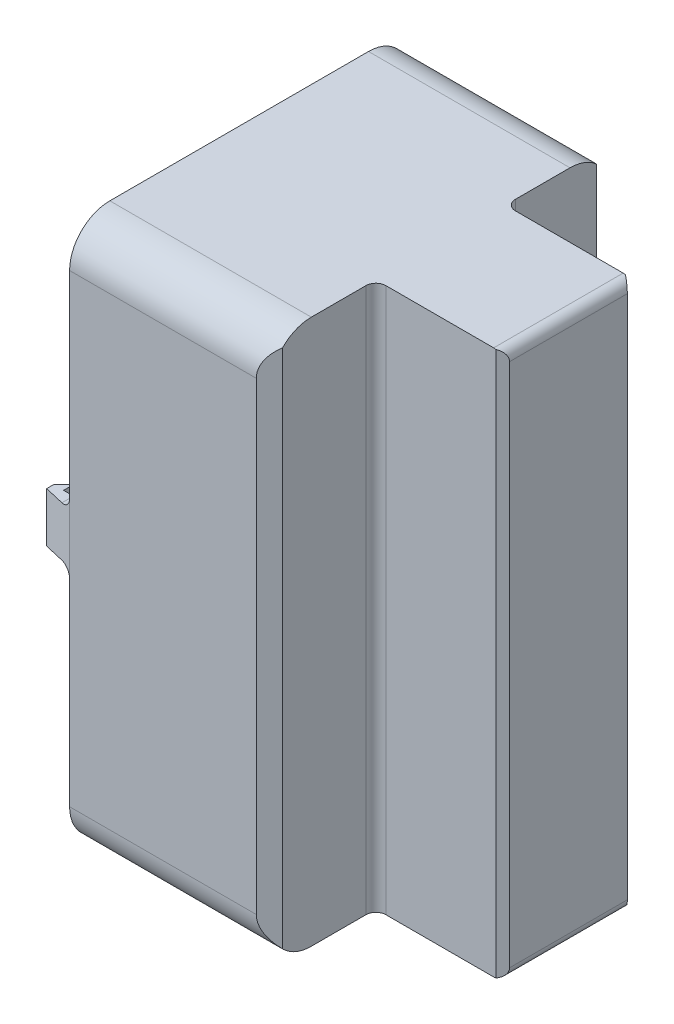
SolidWorks part; units mm, degrees
ref_plane "Top Plane" through (0, 0, 0) normal (0, 0, 1) x (1, 0, 0)
ref_plane "Right Plane" through (0, 0, 0) normal (0, 1, 0) x (1, 0, 0)
ref_plane "Front Plane" through (0, 0, 0) normal (1, 0, 0) x (0, 0, -1)
ref_axis "x-axis" through (-88.99, 0, 0) along (1, 0, 0)
ref_axis "y-axis" through (0, -55, 0) along (0, 1, 0)
ref_axis "z-axis" through (0, 0, 55) along (0, 0, -1)
sketch "Sketch2" plane through (0, 0, 0) normal (1, 0, 0) x (0, -1, 0)
  line L0 (-980.3227, 1369.3053) -> (-980.3227, 1357.3053) construction
  line L1 (-1019.3227, 1357.3053) -> (-1019.3227, 1369.3053) construction
  line L2 (-980.3227, 1357.3053) -> (-1019.3227, 1357.3053) construction
  line L3 (-1018.3227, 1369.3053) -> (-981.3227, 1369.3053) construction
  line L12 (-980.3227, 1369.3053) -> (-980.3227, 1357.3053)
  line L13 (-980.3227, 1357.3053) -> (-1019.3227, 1357.3053)
  line L14 (-1019.3227, 1357.3053) -> (-1019.3227, 1369.3053)
  line L15 (-1019.3227, 1369.3053) -> (-980.3227, 1369.3053)
  line L29 (-1027.1727, 1376.2903) -> (-1027.1727, 1350.3203)
  line L30 (-976.5127, 1380.3303) -> (-1023.1327, 1380.3303)
  line L31 (-972.4727, 1350.3203) -> (-972.4727, 1376.2903)
  line L32 (-1023.1327, 1346.2803) -> (-976.5127, 1346.2803)
  line L33 (-1027.1727, 1376.2903) -> (-1027.1727, 1350.3203)
  line L34 (-976.5127, 1380.3303) -> (-1023.1327, 1380.3303)
  line L35 (-972.4727, 1350.3203) -> (-972.4727, 1376.2903)
  line L36 (-1023.1327, 1346.2803) -> (-976.5127, 1346.2803)
  arc A20 (-1027.1727, 1350.3203) -> (-1023.1327, 1346.2803) centre (-1023.1327, 1350.3203) ccw
  arc A21 (-1023.1327, 1380.3303) -> (-1027.1727, 1376.2903) centre (-1023.1327, 1376.2903) ccw
  arc A22 (-972.4727, 1376.2903) -> (-976.5127, 1380.3303) centre (-976.5127, 1376.2903) ccw
  arc A23 (-976.5127, 1346.2803) -> (-972.4727, 1350.3203) centre (-976.5127, 1350.3203) ccw
  arc A24 (-1027.1727, 1350.3203) -> (-1023.1327, 1346.2803) centre (-1023.1327, 1350.3203) ccw
  arc A25 (-1023.1327, 1380.3303) -> (-1027.1727, 1376.2903) centre (-1023.1327, 1376.2903) ccw
  arc A26 (-972.4727, 1376.2903) -> (-976.5127, 1380.3303) centre (-976.5127, 1376.2903) ccw
  arc A27 (-976.5127, 1346.2803) -> (-972.4727, 1350.3203) centre (-976.5127, 1350.3203) ccw
  dimension "D1" = 1.5
extrude "Boss-Extrude2" add sketch "Sketch2" along normal blind 13 and the other way blind 19.75
sketch "Sketch3" plane through (13, 0, 0) normal (1, 0, 0) x (0, 1, 0)
  line L0 (972.4727, -1350.3203) -> (972.4727, -1376.2903) construction
  line L1 (976.5127, -1380.3303) -> (1023.1327, -1380.3303) construction
  line L2 (1027.1727, -1376.2903) -> (1027.1727, -1350.3203) construction
  line L3 (1023.1327, -1346.2803) -> (976.5127, -1346.2803) construction
  line L4 (972.4727, -1350.3203) -> (972.4727, -1376.2903)
  line L5 (976.5127, -1380.3303) -> (1023.1327, -1380.3303)
  line L7 (1027.1727, -1376.2903) -> (1027.1727, -1350.3203)
  line L13 (1023.1327, -1346.2803) -> (976.5127, -1346.2803)
  arc A0 (976.5127, -1346.2803) -> (972.4727, -1350.3203) centre (976.5127, -1350.3203) ccw construction
  arc A1 (972.4727, -1376.2903) -> (976.5127, -1380.3303) centre (976.5127, -1376.2903) ccw construction
  arc A2 (1023.1327, -1380.3303) -> (1027.1727, -1376.2903) centre (1023.1327, -1376.2903) ccw construction
  arc A3 (1027.1727, -1350.3203) -> (1023.1327, -1346.2803) centre (1023.1327, -1350.3203) ccw construction
  arc A4 (976.5127, -1346.2803) -> (972.4727, -1350.3203) centre (976.5127, -1350.3203) ccw
  arc A6 (972.4727, -1376.2903) -> (976.5127, -1380.3303) centre (976.5127, -1376.2903) ccw
  arc A7 (1023.1327, -1380.3303) -> (1027.1727, -1376.2903) centre (1023.1327, -1376.2903) ccw
  arc A13 (1027.1727, -1350.3203) -> (1023.1327, -1346.2803) centre (1023.1327, -1350.3203) ccw
extrude "Boss-Extrude3" add sketch "Sketch3" along normal blind 0.3
sketch "Sketch6" plane through (-19.75, 0, 0) normal (-1, 0, 0) x (0, -1, 0)
  line L22 (-972.4727, -1363.3053) -> (-1027.1727, -1363.3053) construction
  line L23 (-972.4727, -1350.3203) -> (-972.4727, -1376.2903) construction
  line L24 (-1027.1727, -1376.2903) -> (-1027.1727, -1350.3203) construction
  line L26 (-1025.7727, -1350.3203) -> (-1025.7727, -1376.2903)
  line L27 (-1023.1327, -1378.9303) -> (-976.5127, -1378.9303)
  line L28 (-973.8727, -1376.2903) -> (-973.8727, -1350.3203)
  line L29 (-976.5127, -1347.6803) -> (-1023.1327, -1347.6803)
  arc A32 (-1023.1327, -1347.6803) -> (-1025.7727, -1350.3203) centre (-1023.1327, -1350.3203) ccw
  arc A33 (-1025.7727, -1376.2903) -> (-1023.1327, -1378.9303) centre (-1023.1327, -1376.2903) ccw
  arc A34 (-976.5127, -1378.9303) -> (-973.8727, -1376.2903) centre (-976.5127, -1376.2903) ccw
  arc A35 (-973.8727, -1350.3203) -> (-976.5127, -1347.6803) centre (-976.5127, -1350.3203) ccw
  point P8 (-1025.7727, -1363.3053)
  point P9 (-999.8227, -1378.9303)
  point P10 (-999.8227, -1363.3053)
  dimension "D3" = 2.64
  dimension "D1" = 31.25
  dimension "D2" = 51.9
extrude "Cut-Extrude1" cut sketch "Sketch6" against normal offset from surface (19.727 mm away) 0.1 offset beyond the face yes
ref_plane "Plane1" through (0, 999.8227, 0) normal (0, -1, 0) x (-1, 0, 0)
ref_plane "Plane2" through (0, 0, -1363.3053) normal (0, 0, -1) x (-1, 0, 0)
sketch "Sketch10" plane through (0, 999.8227, 0) normal (0, -1, 0) x (-1, 0, 0)
  line L22 (19.75, 1346.2803) -> (19.75, 1347.6803)
  line L23 (19.75, 1347.6803) -> (21.75, 1347.6803)
  line L24 (21.75, 1347.6803) -> (21.75, 1348.6803)
  line L25 (21.75, 1348.6803) -> (22.75, 1347.6803)
  line L26 (22.75, 1347.6803) -> (22.75, 1346.9803)
  line L27 (22.75, 1346.9803) -> (19.75, 1346.2803)
  line L28 (19.75, 1346.2803) -> (19.75, 1350.3203) construction
  line L30 (19.75, 1346.2803) -> (19.75, 1350.3203) construction
  line L31 (0.023, 1347.6803) -> (19.75, 1347.6803) construction
  point P6 (0, 0)
  point P7 (19.75, 1346.9803)
  point P8 (0, 0)
  point P9 (27.62, -1.5)
  point P12 (24, -0.5115)
  point P13 (21, -1.5)
  point P14 (21, -0.3671)
  point P15 (21, -0.3621)
  point P20 (0, 0)
  dimension "D2" = 3
  dimension "D3" = 1
  dimension "D1" = 1
ref_axis "Axis1" through (0, 999.8227, -1344.5778) along (0, 0, -1)
extrude "Clip Edge" add sketch "Sketch10" along normal mid plane 5
mirror "Mirror1" about plane through (0, 0, -1363.3053) normal (0, 0, -1) of "Clip Edge"
fillet "Fillet1" radius 1 20 edges at (13.3, 973.656, -1379.147) (13.3, 972.4727, -1363.3053) (13.3, 973.656, -1347.4636) (13.3, 999.8227, -1346.2803) (13.3, 1025.9894, -1347.4636) (13.3, 1027.1727, -1363.3053) (13.3, 1025.9894, -1379.147) (13, 999.8227, -1357.3053) (13, 980.3227, -1363.3053) (13, 999.8227, -1369.3053) (13, 1019.3227, -1363.3053) (13.3, 999.8227, -1380.3303) (-0.023, 999.8227, -1369.3053) (-0.023, 980.3227, -1363.3053) (-0.023, 999.8227, -1357.3053) (-0.023, 1019.3227, -1363.3053) (-19.75, 997.3227, -1379.6303) (-19.75, 997.3227, -1346.9803) (-19.75, 1002.3227, -1346.9803) (-19.75, 1002.3227, -1379.6303)
sketch "Sketch11" plane through (0, 1027.1727, 0) normal (0, 1, 0) x (-1, 0, 0)
  line L1 (19.75, -1380.3303) -> (-12.3, -1380.3303) construction
  line L4 (19.75, -1346.2803) -> (-12.3, -1346.2803) construction
  line L5 (-13.3, -1350.3203) -> (-13.3, -1376.2903) construction
  line L6 (19.75, -1380.3303) -> (-12.3, -1380.3303) construction
  line L7 (19.75, -1346.2803) -> (-12.3, -1346.2803) construction
  line L8 (-13.3, -1376.2903) -> (-13.3, -1350.3203) construction
  line L9 (-13.3, -1357.4019) -> (-13.3, -1350.3203)
  line L10 (-12.5325, -1369.8053) -> (-0.477, -1369.8053)
  line L11 (-0.477, -1369.8053) -> (-0.477, -1378.9652)
  line L12 (1.3197, -1380.3303) -> (-12.3, -1380.3303)
  line L13 (-13.3, -1369.2222) -> (-12.5325, -1369.8053)
  line L14 (1.0077, -1346.2803) -> (-12.3, -1346.2803)
  line L15 (-13.3, -1347.2803) -> (-13.3, -1350.3203) construction
  line L16 (-13.3, -1347.2803) -> (-13.3, -1350.3203)
  line L17 (-13.3, -1379.3303) -> (-13.3, -1369.2222)
  line L18 (-0.477, -1378.9652) -> (1.3197, -1380.3303)
  line L19 (-12.5325, -1356.8053) -> (-0.477, -1356.8053)
  line L20 (-0.477, -1356.8053) -> (-0.477, -1347.4344)
  line L21 (-12.5325, -1356.8053) -> (-13.3, -1357.4019)
  line L22 (-0.477, -1347.4344) -> (1.0077, -1346.2803)
  line L23 (0.023, -1350.3203) -> (0.023, -1376.2903) construction
  line L24 (-0.977, -1357.3053) -> (-12, -1357.3053) construction
  line L25 (-0.977, -1369.3053) -> (-12, -1369.3053) construction
  arc A2 (-13.3, -1379.3303) -> (-12.3, -1380.3303) centre (-12.3, -1379.3303) ccw construction
  arc A3 (-13.3, -1379.3303) -> (-12.3, -1380.3303) centre (-12.3, -1379.3303) ccw
  arc A5 (-12.3, -1346.2803) -> (-13.3, -1347.2803) centre (-12.3, -1347.2803) ccw construction
  arc A6 (-12.3, -1346.2803) -> (-13.3, -1347.2803) centre (-12.3, -1347.2803) ccw
  point P20 (-12.5325, -1369.8053)
  point P21 (-0.477, -1378.9652)
  dimension "D1" = 0.5
  dimension "D2" = 0.5
  dimension "D3" = 0.5
extrude "Cut-Extrude2" cut sketch "Sketch11" against normal through all
fillet "Fillet2" radius 1 2 edges at (0.477, 999.8227, -1356.8053) (0.477, 999.8227, -1369.8053)
